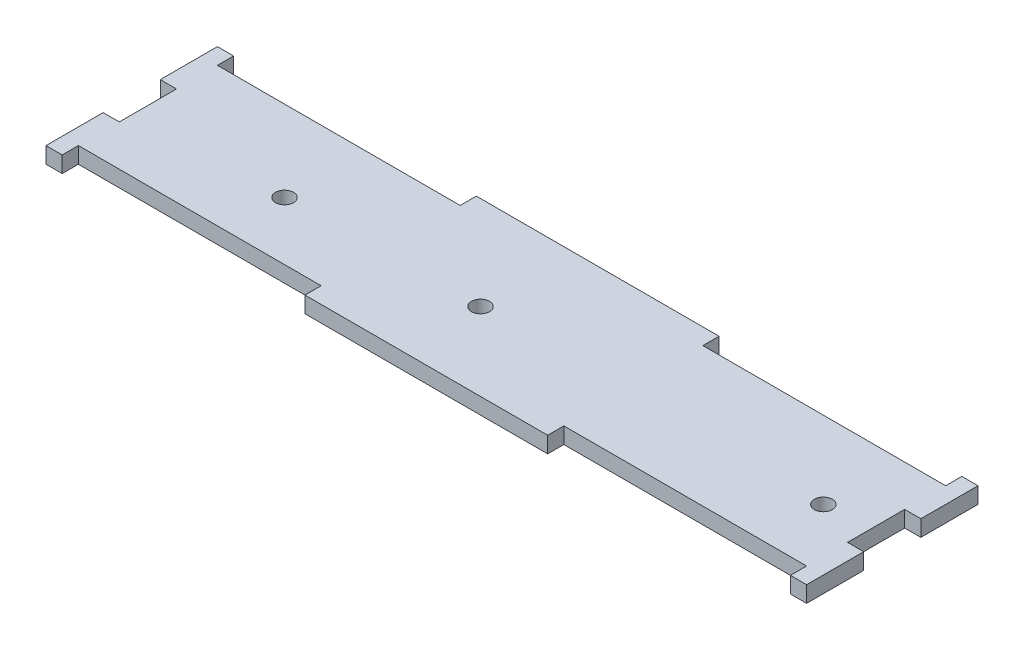
SolidWorks part; units mm, degrees
ref_plane "Front Plane" through (0, 0, 0) normal (0, 0, 1) x (1, 0, 0)
ref_plane "Top Plane" through (0, 0, 0) normal (0, 1, 0) x (1, 0, 0)
ref_plane "Right Plane" through (0, 0, 0) normal (1, 0, 0) x (0, 0, -1)
sketch "Sketch1" plane through (0, 0, 0) normal (0, 1, 0) x (1, 0, 0)
  line L2 (0, 0) -> (0, 15.2)
  line L6 (4, 2.8333) -> (4, 12.3667)
  line L8 (-117.5, 12.3667) -> (-117.5, 2.8333)
  line L11 (6.7, -6.7) -> (4, -6.7)
  line L12 (-111.5, -4) -> (-111.5, 19.2) construction
  line L13 (-117.5, -6.7) -> (-120.2, -6.7)
  line L14 (-120.2, 21.9) -> (-120.2, 12.3667)
  line L17 (6.7, -6.7) -> (6.7, 2.8333)
  line L18 (0, 15.2) -> (-107.5, 15.2) construction
  line L19 (-107.5, 0) -> (-107.5, 15.2) construction
  line L20 (0, 0) -> (-107.5, 0) construction
  line L21 (-111.5, -4) -> (-117.5, -4) construction
  line L22 (4, -4) -> (-111.5, -4) construction
  line L23 (-117.5, -4) -> (-77, -4)
  line L25 (-120.2, 21.9) -> (-120.2, -6.7) construction
  line L26 (-120.2, 2.8333) -> (-120.2, -6.7)
  line L28 (-36.5, -4) -> (4, -4)
  line L29 (-120.2, 2.8333) -> (-117.5, 2.8333)
  line L30 (-120.2, 12.3667) -> (-117.5, 12.3667)
  line L31 (-77, -4) -> (-77, -6.7)
  line L32 (-36.5, -4) -> (-36.5, -6.7)
  line L33 (-117.5, -4) -> (-117.5, -6.7)
  line L34 (-117.5, 19.2) -> (-117.5, 21.9)
  line L35 (-117.5, 19.2) -> (-117.5, -4) construction
  line L36 (-111.5, -6.7) -> (-120.2, -6.7) construction
  line L37 (6.7, -6.7) -> (-111.5, -6.7) construction
  line L39 (6.7, -6.7) -> (6.7, 21.9) construction
  line L40 (6.7, 12.3667) -> (6.7, 21.9)
  line L41 (6.7, 12.3667) -> (4, 12.3667)
  line L42 (6.7, 2.8333) -> (4, 2.8333)
  line L43 (4, -4) -> (4, -6.7)
  line L44 (4, 19.2) -> (4, 21.9)
  line L45 (4, -4) -> (4, 19.2) construction
  line L46 (-36.5, -6.7) -> (-77, -6.7)
  line L47 (4, 19.2) -> (-111.5, 19.2) construction
  line L48 (-111.5, 19.2) -> (-117.5, 19.2) construction
  line L49 (6.7, 21.9) -> (-111.5, 21.9) construction
  line L50 (-111.5, 21.9) -> (-120.2, 21.9) construction
  line L51 (-120.2, 21.9) -> (-117.5, 21.9)
  line L52 (6.7, 21.9) -> (4, 21.9)
  line L54 (-36.5, 19.2) -> (4, 19.2)
  line L55 (-36.5, 19.2) -> (-36.5, 21.9)
  line L56 (-36.5, 21.9) -> (-77, 21.9)
  line L57 (-77, 19.2) -> (-77, 21.9)
  line L58 (-117.5, 19.2) -> (-77, 19.2)
  circle A0 centre (-3.5, 6.3) radius 1.5
  circle A1 centre (-60.7, 6.3) radius 1.5
  circle A2 centre (-92.8, 5.7) radius 1.5
  point P7 (-12.4, 6.1)
  point P8 (-52.4, 6.1)
  point P9 (-34.4, 6.1)
  point P10 (-70.4, 6.1)
  point P11 (-88.4, 6.1)
  dimension "D3" = 12.4
  dimension "D9" = 60.7
  dimension "D5" = 34.4
  dimension "D6" = 52.4
  dimension "D7" = 70.4
  dimension "D8" = 88.4
  dimension "D14" = 96.8
  dimension "D11" = 4
  dimension "D15" = 2.7
extrude "Boss-Extrude1" add sketch "Sketch1" along normal blind 2.7 contours L58 L34 L51 L14 L30 L8 L29 L26 L13 L33 L23 L31 L46 L32 L28 L43 L11 L17 L42 L6 L41 L40 L52 L44 L54 L55 L56 L57 A2 A1 A0 region at (-56.78, 0, -7.6102)
